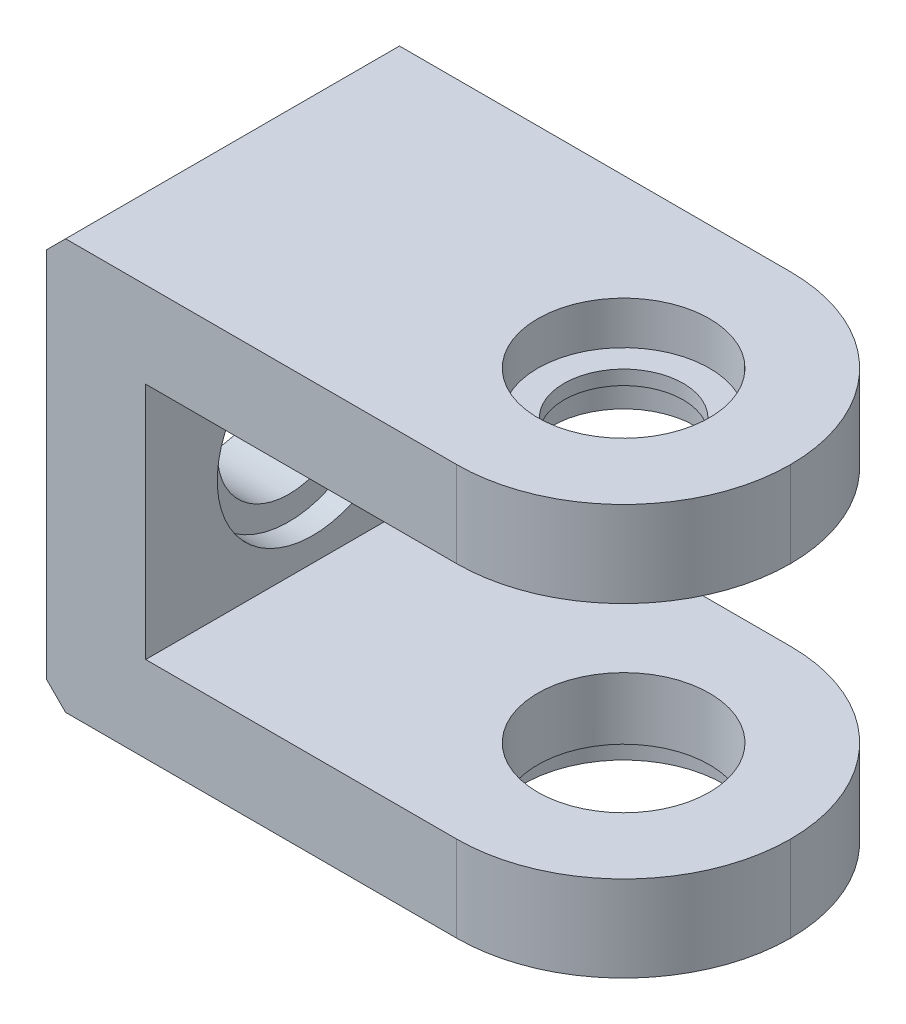
SolidWorks part; units mm, degrees
ref_plane "Přední rovina" through (0, 0, 0) normal (0, 0, 1) x (1, 0, 0)
ref_plane "Vrchní rovina" through (0, 0, 0) normal (0, 1, 0) x (1, 0, 0)
ref_plane "Pravá rovina" through (0, 0, 0) normal (1, 0, 0) x (0, 0, -1)
sketch "Skica2" plane through (0, 0, 0) normal (0, 0, 1) x (1, 0, 0)
  line L0 (0, 0) -> (-121, 0)
  line L6 (-100.2008, -18) -> (0, -18)
  line L7 (0, -18) -> (0, 0)
  line L10 (-121, 0) -> (-121, -86)
  line L11 (-121, -43) -> (-100.2008, -43) construction
  line L12 (-100.2008, -68) -> (-100.2008, -18)
  line L13 (0, -68) -> (0, -86)
  line L14 (-100.2008, -68) -> (0, -68)
  line L15 (0, -86) -> (-121, -86)
  point P1 (-51.181, 0)
  point P3 (0, 0)
  point P6 (0, 0)
  point P10 (-51.181, -86)
  dimension "D4" = 121
  dimension "D1" = 86
  dimension "D2" = 18
  dimension "D3" = 20.7992
extrude "Přidat vysunutím1" add sketch "Skica2" along normal blind 70 contours L6 L7 L0 L10 L15 L13 L14 L12
fillet "Zaoblit1" radius 35 4 edges at (0, -77, 70) (0, -77, 0) (0, -9, 70) (0, -9, 0)
sketch "Skica3" plane through (-121, 0, 0) normal (-1, 0, 0) x (0, 0, 1)
  line L0 (0, -43) -> (70, -43) construction
  line L1 (0, 0) -> (0, -86) construction
  line L2 (70, 0) -> (70, -86) construction
  line L3 (35, 0) -> (35, -86) construction
  line L4 (70, -86) -> (0, -86) construction
  circle A0 centre (35, -43) radius 15
  dimension "D1" = 30
extrude "Odebrat vysunutím2" cut sketch "Skica3" against normal up to next
sketch "Skica5" plane through (-100.2008, 0, 0) normal (1, 0, 0) x (0, 0, -1)
  line L0 (-70, -43) -> (0, -43) construction
  line L1 (-70, -68) -> (-70, -18) construction
  line L2 (0, -68) -> (0, -18) construction
  line L3 (-35, -18) -> (-35, -68) construction
  line L4 (-70, -68) -> (0, -68) construction
  circle A0 centre (-35, -43) radius 20
  dimension "D1" = 40
extrude "Odebrat vysunutím3" cut sketch "Skica5" against normal blind 5
sketch "Skica6" plane through (0, 0, 0) normal (0, 1, 0) x (1, 0, 0)
  line L0 (-35, 0) -> (-35, -70) construction
  line L1 (0, -35) -> (-121, -35) construction
  line L2 (-121, -70) -> (-121, 0) construction
  circle A0 centre (-35, -35) radius 12.5
  dimension "D1" = 25
extrude "Odebrat vysunutím4" cut sketch "Skica6" against normal up to next
sketch "Skica7" plane through (0, 0, 0) normal (0, 1, 0) x (1, 0, 0)
  circle A0 centre (-35, -35) radius 18
  dimension "D1" = 36
extrude "Odebrat vysunutím5" cut sketch "Skica7" against normal blind 9
sketch "Skica8" plane through (0, -18, 0) normal (0, -1, 0) x (1, 0, 0)
  circle A0 centre (-35, 35) radius 15
  dimension "D1" = 30
extrude "Odebrat vysunutím6" cut sketch "Skica8" against normal blind 6
sketch "Skica9" plane through (0, -86, 0) normal (0, -1, 0) x (1, 0, 0)
  line L0 (-35, 70) -> (-35, 0) construction
  line L1 (0, 35) -> (-121, 35) construction
  line L2 (-121, 70) -> (-121, 0) construction
  circle A0 centre (-35, 35) radius 18
  dimension "D1" = 36
extrude "Odebrat vysunutím7" cut sketch "Skica9" against normal up to next
sketch "Skica10" plane through (0, -86, 0) normal (0, -1, 0) x (1, 0, 0)
  circle A0 centre (-35, 35) radius 21
  dimension "D1" = 42
extrude "Odebrat vysunutím8" cut sketch "Skica10" against normal blind 5
chamfer "Zkosení1" distance 4 angle 45 2 edges at (-121, -86, 35) (-121, 0, 35)
